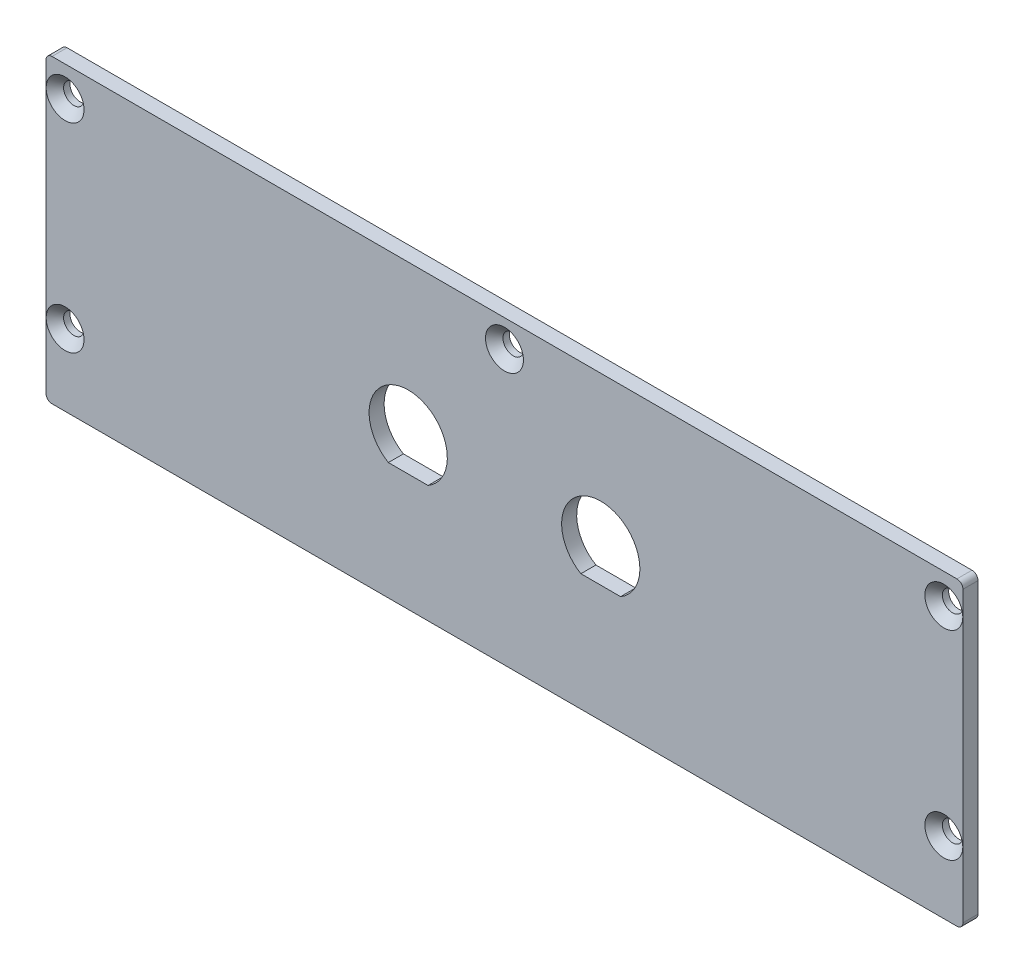
SolidWorks part; units mm, degrees
material "6063-T6"
ref_plane "Front Plane" through (0, 0, 0) normal (0, 0, 1) x (1, 0, 0)
ref_plane "Top Plane" through (0, 0, 0) normal (0, 1, 0) x (1, 0, 0)
ref_plane "Right Plane" through (0, 0, 0) normal (1, 0, 0) x (0, 0, -1)
sketch "Sketch2" plane through (0, 0, 0) normal (0, 0, 1) x (1, 0, 0)
  line L0 (-75.2, -11.5598) -> (75.2, -11.5598)
  line L1 (-75.2, 38.4402) -> (75.2, 38.4402)
  line L2 (-76.2, 37.4402) -> (-76.2, -10.5598)
  line L4 (76.2, 37.4402) -> (76.2, -10.5598)
  line L5 (-76.2, 38.4402) -> (76.2, -37.7598) construction
  line L6 (-76.2, -37.7598) -> (76.2, 38.4402) construction
  arc A0 (76.2, -10.5598) -> (75.2, -11.5598) centre (75.2, -10.5598) cw
  arc A1 (-75.2, -11.5598) -> (-76.2, -10.5598) centre (-75.2, -10.5598) cw
  arc A6 (76.2, 37.4402) -> (75.2, 38.4402) centre (75.2, 37.4402) ccw
  arc A7 (-75.2, 38.4402) -> (-76.2, 37.4402) centre (-75.2, 37.4402) ccw
  dimension "D2" = 1
  dimension "D1" = 152.4
  dimension "D3" = 50
extrude "Boss-Extrude1" add sketch "Sketch2" along normal blind 2.5
hole_wizard "CSK for M3 Countersunk Flat Head Screw1" positions "Sketch4" profile "Sketch5" countersink size "M3" standard "ISO" end condition through all
sketch "Sketch4" plane through (0, 0, 2.5) normal (0, 0, 1) x (1, 0, 0)
  point P0 (-73.025, 33.4402)
  point P2 (-73.025, 0.3402)
  point P4 (0, 33.9152)
  point P6 (73.025, 33.4402)
  point P8 (73.025, 0.3402)
sketch "Sketch5" plane through (-73.025, 33.4402, 2.5) normal (1, 0, 0) x (0, -1, 0)
  line L0 (0, 0) -> (0, 2.5)
  line L1 (0, 2.5) -> (1.7, 2.5)
  line L2 (1.7, 2.5) -> (1.7, 1.45)
  line L3 (1.7, 1.45) -> (3.15, 0)
  line L5 (3.15, 0) -> (0, 0)
  line L6 (-1.7, 1.45) -> (-3.15, 0) construction
  line L11 (0, -6.35) -> (0, 107.95) construction
  dimension "Thru Hole Dia." = 3.4
  dimension "Thru Hole Depth" = 2.5
  dimension "Near C'Sink Dia." = 6.3
  dimension "Near C'Sink Angle" = 90
sketch "Sketch6" plane through (0, 0, 2.5) normal (0, 0, 1) x (1, 0, 0)
  line L2 (-19.3, 7.9356) -> (-12.7, 7.9356)
  line L3 (12.7, 7.9356) -> (19.3, 7.9356)
  circle A0 centre (0, 33.9152) radius 1.7 construction
  circle A1 centre (-16, 13.5356) radius 6.5
  circle A2 centre (16, 13.5356) radius 6.5
  point P0 (-16, 7.9356)
  point P3 (0.1802, 13.3166)
  dimension "D1" = 13
  dimension "D2" = 5.6
  dimension "D3" = 16
extrude "Cut-Extrude1" cut sketch "Sketch6" against normal through all contours L2 A1 | L3 A2 region at (-16, 13.7217, 2.5) region at (16, 13.7217, 2.5)
